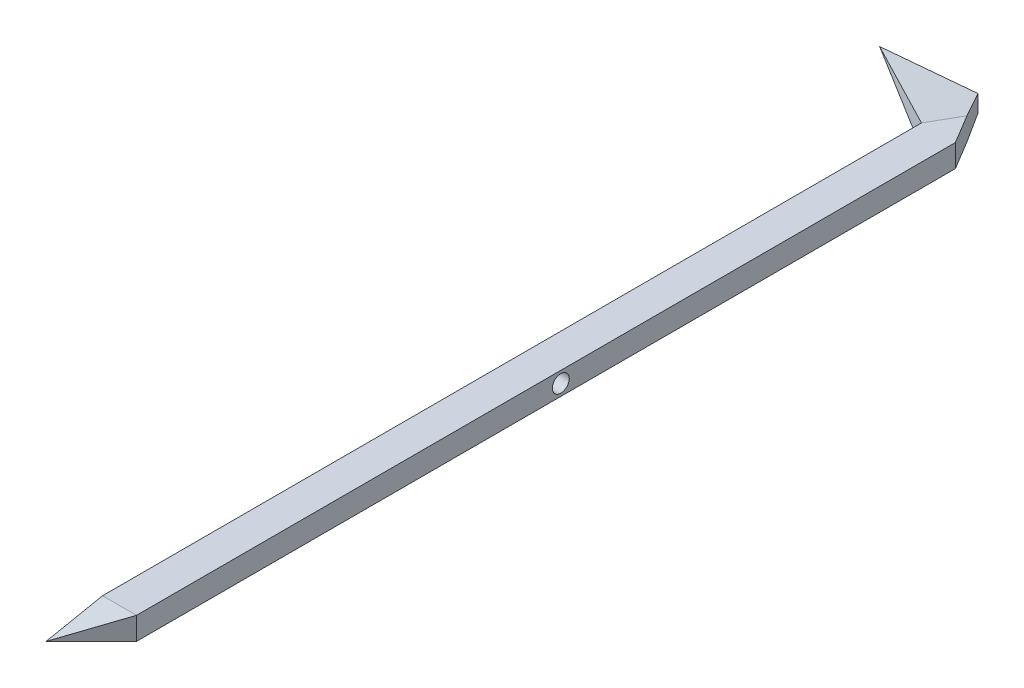
SolidWorks part; units mm, degrees
ref_plane "Front Plane" through (0, 0, 0) normal (0, 0, 1) x (1, 0, 0)
ref_plane "Top Plane" through (0, 0, 0) normal (0, 1, 0) x (1, 0, 0)
ref_plane "Right Plane" through (0, 0, 0) normal (1, 0, 0) x (0, 0, -1)
sketch "Sketch1" plane through (0, 0, 0) normal (0, 1, 0) x (1, 0, 0)
  line L0 (0, 104.6861) -> (0, -104.6861)
  line L1 (0, -104.6861) -> (7.62, -91.9861)
  line L2 (7.62, -91.9861) -> (7.62, 91.9861)
  line L3 (7.62, 91.9861) -> (0, 104.6861)
  line L4 (0, 104.6861) -> (-22.098, 104.6861)
  line L5 (-22.098, 104.6861) -> (0, 91.9861)
  line L6 (0, 91.9861) -> (0, 104.6861)
  line L7 (0, 3.3401) -> (-25.4, 3.3401)
  line L8 (7.62, 3.3401) -> (33.02, 3.3401)
  point P4 (0, 0)
  dimension "D1" = 209.3722
  dimension "D2" = 12.7
  dimension "D3" = 12.7
  dimension "D4" = 7.62
  dimension "D5" = 22.098
  dimension "D6" = 101.346
  dimension "D7" = 25.4
  dimension "D8" = 25.4
extrude "Boss-Extrude1" add sketch "Sketch1" along normal blind 5.08 contours L2 L3 L0 L1 | L4 L5 L0 region at (3.728, 0, 0) region at (-7.366, 0, -100.4528)
sketch "Sketch2" plane through (7.62, 0, 0) normal (1, 0, 0) x (0, 0, -1)
  line L0 (-91.9861, 5.08) -> (-104.6861, 2.54)
  line L1 (-104.6861, 5.08) -> (-104.6861, 0) construction
  line L2 (-104.6861, 2.54) -> (-91.9861, 0)
  line L3 (-91.9861, 0) -> (-104.6861, 0)
  line L4 (-104.6861, 0) -> (-104.6861, 2.54)
  line L5 (-104.6861, 5.08) -> (-91.9861, 5.08)
  line L6 (-104.6861, 5.08) -> (-104.6861, 2.54)
extrude "Cut-Extrude1" cut sketch "Sketch2" along normal through all both and the other way through all contours L5 L6 L0 | L4 L3 L2 region at (7.62, 0.8467, 100.4528) region at (7.62, 4.2333, 100.4528)
sketch "Sketch3" plane through (39.7397, 0, -69.1472) normal (-0.4983, 0, 0.867) x (0.867, 0, 0.4983)
  line L0 (-45.8352, 5.08) -> (-71.3227, 2.54)
  line L1 (-71.3227, 5.08) -> (-71.3227, 0) construction
  line L2 (-71.3227, 2.54) -> (-45.8352, 0)
  line L3 (-45.8352, 0) -> (-71.3227, 0)
  line L4 (-71.3227, 0) -> (-71.3227, 2.54)
  line L5 (-45.8352, 5.08) -> (-71.3227, 5.08)
  line L6 (-71.3227, 5.08) -> (-71.3227, 2.54)
  line M1 (-71.3227, 0) -> (-45.8352, 0)
  line M3 (-45.8352, 5.08) -> (-71.3227, 5.08)
  line M4 (-71.3227, 5.08) -> (-71.3227, 0)
extrude "Cut-Extrude2" cut sketch "Sketch3" against normal through all both and the other way through all contours L0 M3 M4 | L2 M4 M1 region at (-14.732, 0.8467, -100.4528) region at (-14.732, 4.2333, -100.4528)
sketch "Sketch4" plane through (0, 0, 0) normal (-1, 0, 0) x (0, 0, 1)
  circle A0 centre (-3.3401, 2.54) radius 1.905
  dimension "D2" = 3.81
  dimension "D1" = 101.346
extrude "Cut-Extrude3" cut sketch "Sketch4" against normal blind 21.336
